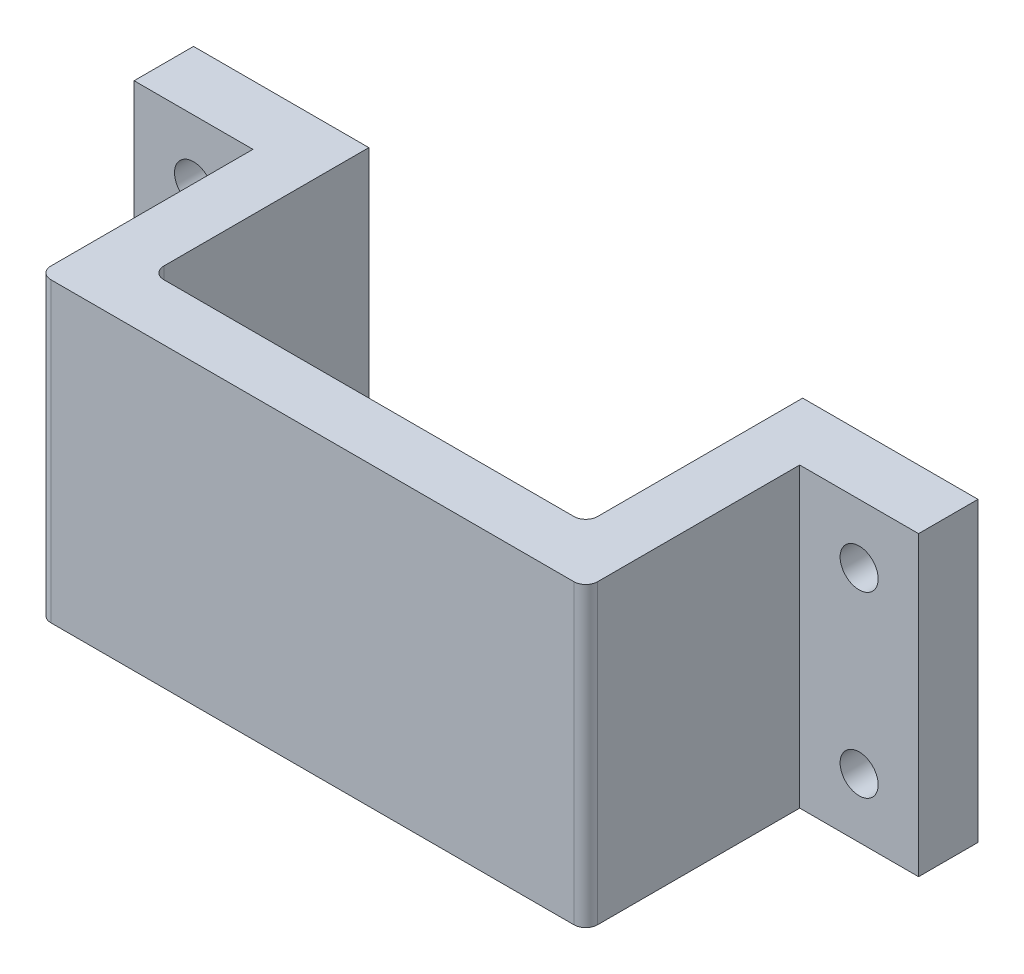
SolidWorks part; units mm, degrees
material "PBT Общее назначение"
ref_plane "Спереди" through (0, 0, 0) normal (0, 0, 1) x (1, 0, 0)
ref_plane "Сверху" through (0, 0, 0) normal (0, 1, 0) x (1, 0, 0)
ref_plane "Справа" through (0, 0, 0) normal (1, 0, 0) x (0, 0, -1)
sketch "Эскиз1" plane through (0, 0, 0) normal (0, 1, 0) x (1, 0, 0)
  line L0 (0, 0) -> (46, 0)
  line L1 (0, 0) -> (0, 23)
  line L2 (46, 0) -> (46, 23)
  line L3 (4.75, 23) -> (0, 23)
  line L5 (4.75, 23) -> (4.75, 4.75)
  line L6 (41.25, 23) -> (41.25, 4.75)
  line L7 (4.75, 4.75) -> (41.25, 4.75)
  line L9 (46, 23) -> (41.25, 23)
  line L12 (23, 23) -> (23, 0) construction
  dimension "D1" = 23
  dimension "D2" = 4.75
  dimension "D3" = 18.25
  dimension "D4" = 36.5
  dimension "D5" = 4.75
  dimension "D6" = 4.75
extrude "Бобышка-Вытянуть1" add sketch "Эскиз1" along normal blind 25
sketch "Эскиз2" plane through (0, 0, -23) normal (0, 0, -1) x (-1, 0, 0)
  line L0 (-46, 25) -> (-46, 0)
  line L1 (-46, 25) -> (-56, 25)
  line L2 (-46, 0) -> (-56, 0)
  line L3 (-56, 25) -> (-56, 0)
  line L4 (0, 25) -> (0, 0)
  line L5 (0, 25) -> (10, 25)
  line L6 (0, 0) -> (10, 0)
  line L7 (10, 25) -> (10, 0)
  dimension "D1" = 10
  dimension "D2" = 10
extrude "Бобышка-Вытянуть2" add sketch "Эскиз2" against normal blind 5
fillet "Скругление1" radius 1 2 edges at (41.25, 12.5, -4.75) (4.75, 12.5, -4.75)
sketch "Эскиз3" plane through (0, 0, -23) normal (0, 0, -1) x (-1, 0, 0)
  circle A0 centre (5, 20) radius 1.6 construction
  circle A1 centre (5, 20) radius 1.6
  circle A2 centre (5, 5) radius 1.6 construction
  circle A3 centre (5, 5) radius 1.6
  circle A4 centre (-51, 20) radius 1.6 construction
  circle A5 centre (-51, 20) radius 1.6
  circle A6 centre (-51, 5) radius 1.6 construction
  circle A7 centre (-51, 5) radius 1.6
extrude "Вырез-Вытянуть1" cut sketch "Эскиз3" against normal through all
fillet "Скругление2" radius 1 2 edges at (0, 12.5, 0) (46, 12.5, 0)
